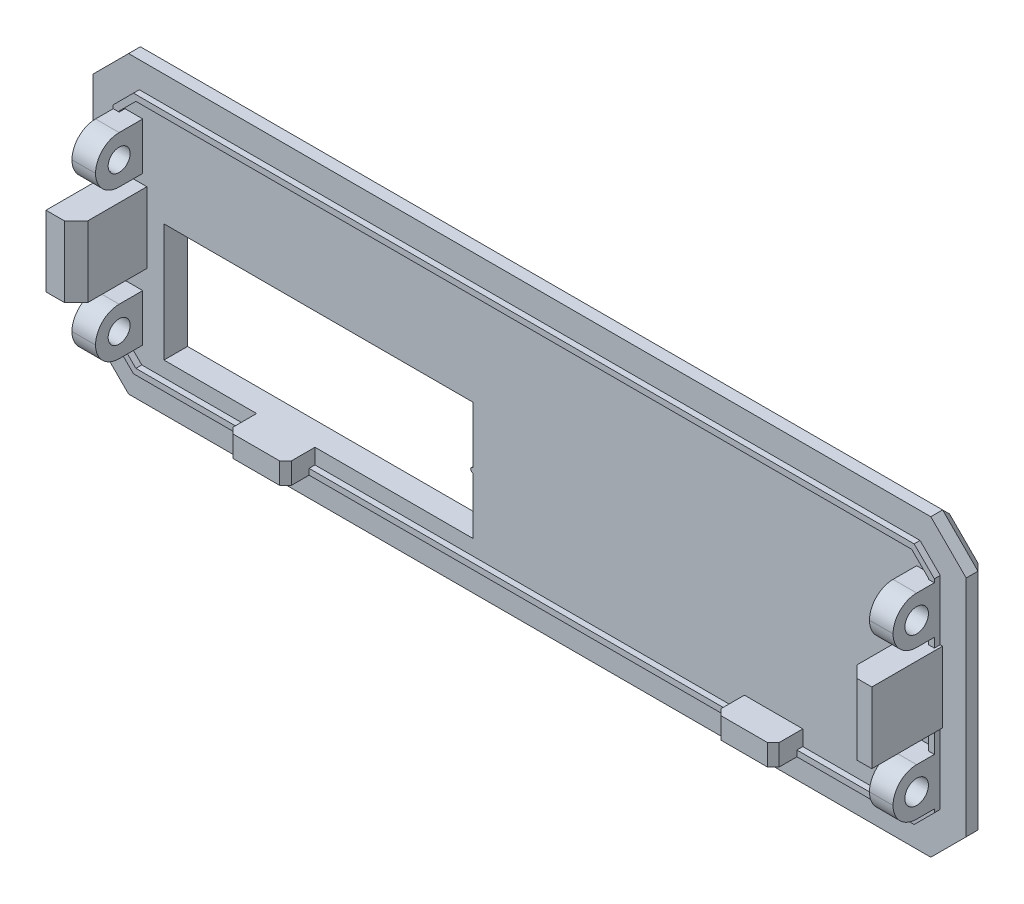
SolidWorks part; units mm, degrees
ref_plane "前视基准面" through (0, 0, 0) normal (0, 0, 1) x (1, 0, 0)
ref_plane "上视基准面" through (0, 0, 0) normal (0, 1, 0) x (1, 0, 0)
ref_plane "右视基准面" through (0, 0, 0) normal (1, 0, 0) x (0, 0, -1)
other "Configuration Table"
sketch "草图1" plane through (0, 0, 0) normal (0, 0, 1) x (1, 0, 0)
  line L0 (-39.7638, 4.7992) -> (-36.7638, 7.7992)
  line L5 (-36.7638, 7.7992) -> (31.2362, 7.7992)
  line L6 (-39.7638, 4.7992) -> (-39.7638, -14.2008)
  line L7 (-36.7638, -17.2008) -> (31.2362, -17.2008)
  line L8 (34.2362, 4.7992) -> (34.2362, -14.2008)
  line L9 (-39.7638, -14.2008) -> (-36.7638, -17.2008)
  line L10 (31.2362, -17.2008) -> (34.2362, -14.2008)
  line L11 (31.2362, 7.7992) -> (34.2362, 4.7992)
  point P0 (-39.7638, 7.7992)
  point P1 (34.2362, -17.2008)
  point P2 (-39.7638, -17.2008)
  point P3 (34.2362, 7.7992)
  dimension "D1" = 74
  dimension "D2" = 25
extrude "凸台-拉伸1" add sketch "草图1" along normal blind 2
chamfer "倒角1" distance 1 angle 45 8 edges at (-38.2638, 6.2992, 0) (-2.7638, -17.2008, 0) (-39.7638, -4.7008, 0) (-38.2638, -15.7008, 0) (32.7362, -15.7008, 0) (34.2362, -4.7008, 0) (32.7362, 6.2992, 0) (-2.7638, 7.7992, 0)
sketch "草图3" plane through (0, 0, 2) normal (0, 0, 1) x (1, 0, 0)
  line L0 (-36.7638, 7.7992) -> (31.2362, 7.7992) construction
  line L1 (-37.5638, 3.5992) -> (-35.5638, 3.5992)
  line L2 (-37.5638, 3.5992) -> (-37.5638, -0.4008)
  line L3 (-37.5638, -0.4008) -> (-35.5638, -0.4008)
  line L4 (-35.5638, 3.5992) -> (-35.5638, -0.4008)
  line L5 (-37.5638, -13.0008) -> (-35.5638, -13.0008)
  line L6 (-37.5638, -13.0008) -> (-37.5638, -9.0008)
  line L7 (-37.5638, -9.0008) -> (-35.5638, -9.0008)
  line L8 (-35.5638, -13.0008) -> (-35.5638, -9.0008)
  line L9 (32.0362, 3.5992) -> (30.0362, 3.5992)
  line L10 (32.0362, 3.5992) -> (32.0362, -0.4008)
  line L11 (32.0362, -0.4008) -> (30.0362, -0.4008)
  line L12 (30.0362, 3.5992) -> (30.0362, -0.4008)
  line L13 (32.0362, -13.0008) -> (30.0362, -13.0008)
  line L14 (32.0362, -13.0008) -> (32.0362, -9.0008)
  line L15 (32.0362, -9.0008) -> (30.0362, -9.0008)
  line L16 (30.0362, -13.0008) -> (30.0362, -9.0008)
  line L17 (-39.7638, -14.2008) -> (-39.7638, 4.7992) construction
  line L18 (34.2362, 4.7992) -> (34.2362, -14.2008) construction
  line L19 (31.2362, -17.2008) -> (-36.7638, -17.2008) construction
  dimension "D1" = 2
  dimension "D2" = 4
  dimension "D3" = 4.2
  dimension "D4" = 2.2
  dimension "D5" = 2.2
  dimension "D6" = 4.2
extrude "凸台-拉伸2" add sketch "草图3" along normal blind 4
fillet "圆角1" radius 2 8 edges at (31.0362, 3.5992, 6) (31.0362, -0.4008, 6) (31.0362, -9.0008, 6) (31.0362, -13.0008, 6) (-36.5638, -13.0008, 6) (-36.5638, -9.0008, 6) (-36.5638, 3.5992, 6) (-36.5638, -0.4008, 6)
sketch "草图4" plane through (32.0362, 0, 0) normal (1, 0, 0) x (0, 0, -1)
  circle A0 centre (-4, 1.5992) radius 1
  circle A1 centre (-4, -11.0008) radius 1
  dimension "D1" = 2
extrude "切除-拉伸1" cut sketch "草图4" against normal up to next (2 mm away) draft 2
sketch "草图5" plane through (-37.5638, 0, 0) normal (-1, 0, 0) x (0, 0, 1)
  circle A0 centre (4, 1.5992) radius 1
  circle A1 centre (4, -11.0008) radius 1
  dimension "D1" = 2
extrude "切除-拉伸2" cut sketch "草图5" against normal up to next (2 mm away) draft 2
sketch "草图8" plane through (0, 0, 2) normal (0, 0, 1) x (1, 0, 0)
  line L0 (-37.7638, 3.9708) -> (-37.7638, -13.3724) construction
  line L1 (-37.7638, -1.2008) -> (-35.2138, -1.2008)
  line L2 (-37.7638, -1.2008) -> (-37.7638, -7.2008)
  line L3 (-37.7638, -7.2008) -> (-35.2138, -7.2008)
  line L4 (-35.2138, -1.2008) -> (-35.2138, -7.2008)
  line L6 (32.2362, -13.3724) -> (32.2362, 3.9708) construction
  line L7 (32.2362, -1.2008) -> (29.9862, -1.2008)
  line L8 (32.2362, -1.2008) -> (32.2362, -7.2008)
  line L9 (32.2362, -7.2008) -> (29.9862, -7.2008)
  line L10 (29.9862, -1.2008) -> (29.9862, -7.2008)
  line L12 (-36.7638, -17.2008) -> (31.2362, -17.2008) construction
  dimension "D1" = 10
  dimension "D2" = 6
  dimension "D3" = 2.55
  dimension "D4" = 2.25
extrude "凸台-拉伸5" add sketch "草图8" along normal blind 6
chamfer "倒角3" distance 1 angle 45 2 edges at (29.9862, -4.2008, 8) (-35.2138, -4.2008, 8)
sketch "草图10" plane through (0, 0, 0) normal (0, 0, -1) x (-1, 0, 0)
  line L0 (36.7638, -17.2008) -> (-31.2362, -17.2008) construction
  line L1 (7.5638, -3.2008) -> (33.7638, -3.2008)
  line L2 (7.5638, -3.2008) -> (7.5638, -13.2008)
  line L3 (7.5638, -13.2008) -> (33.7638, -13.2008)
  line L4 (33.7638, -3.2008) -> (33.7638, -13.2008)
  line L5 (39.7638, 4.7992) -> (39.7638, -14.2008) construction
  dimension "D1" = 4
  dimension "D2" = 10
  dimension "D3" = 6
  dimension "D4" = 26.2
extrude "切除-拉伸3" cut sketch "草图10" against normal up to next
sketch "草图11" plane through (0, 0, 2) normal (0, 0, 1) x (1, 0, 0)
  line L8 (30.1178, 5.0992) -> (-35.6455, 5.0992)
  line L9 (-35.6455, 5.0992) -> (-37.0638, 3.6808)
  line L10 (-37.0638, 3.6808) -> (-37.0638, -13.0824)
  line L11 (-37.0638, -13.0824) -> (-35.6455, -14.5008)
  line L12 (-35.6455, -14.5008) -> (30.1178, -14.5008)
  line L13 (30.1178, -14.5008) -> (31.5362, -13.0824)
  line L14 (31.5362, -13.0824) -> (31.5362, 3.6808)
  line L15 (31.5362, 3.6808) -> (30.1178, 5.0992)
  line L16 (30.3249, 5.5992) -> (-35.8526, 5.5992)
  line L17 (-35.8526, 5.5992) -> (-37.5638, 3.8879)
  line L18 (-37.5638, 3.8879) -> (-37.5638, -13.2895)
  line L19 (-37.5638, -13.2895) -> (-35.8526, -15.0008)
  line L20 (-35.8526, -15.0008) -> (30.3249, -15.0008)
  line L21 (30.3249, -15.0008) -> (32.0362, -13.2895)
  line L22 (32.0362, -13.2895) -> (32.0362, 3.8879)
  line L23 (32.0362, 3.8879) -> (30.3249, 5.5992)
  line L24 (30.3249, 5.5992) -> (-35.8526, 5.5992)
  line L25 (-35.8526, 5.5992) -> (-37.5638, 3.8879)
  line L26 (-37.5638, 3.8879) -> (-37.5638, -13.2895)
  line L27 (-37.5638, -13.2895) -> (-35.8526, -15.0008)
  line L28 (-35.8526, -15.0008) -> (30.3249, -15.0008)
  line L29 (30.3249, -15.0008) -> (32.0362, -13.2895)
  line L30 (32.0362, -13.2895) -> (32.0362, 3.8879)
  line L31 (32.0362, 3.8879) -> (30.3249, 5.5992)
  dimension "D1" = 2.2
  dimension "D2" = 0.5
extrude "凸台-拉伸7" add sketch "草图11" along normal blind 0.5
sketch "草图12" plane through (0, 0, 2) normal (0, 0, 1) x (1, 0, 0)
  line L0 (20.4077, -13.2008) -> (15.4077, -13.2008) construction
  line L1 (15.4362, -13.2008) -> (20.3862, -13.2008)
  line L2 (15.4362, -13.2008) -> (15.4362, -15.0008)
  line L3 (15.4362, -15.0008) -> (20.3862, -15.0008)
  line L4 (20.3862, -13.2008) -> (20.3862, -15.0008)
  line L6 (34.2362, -14.2008) -> (34.2362, 4.7992) construction
  line L7 (-33.7638, -13.2008) -> (-7.5638, -13.2008) construction
  line L8 (-25.9138, -13.2008) -> (-20.9638, -13.2008)
  line L9 (-25.9138, -13.2008) -> (-25.9138, -15.0008)
  line L10 (-25.9138, -15.0008) -> (-20.9638, -15.0008)
  line L11 (-20.9638, -13.2008) -> (-20.9638, -15.0008)
  line L13 (-39.7638, 4.7992) -> (-39.7638, -14.2008) construction
  line L14 (-35.8526, -15.0008) -> (30.3249, -15.0008) construction
  dimension "D1" = 13.85
  dimension "D2" = 4.95
  dimension "D3" = 13.85
extrude "凸台-拉伸8" add sketch "草图12" along normal blind 2.5
chamfer "倒角4" distance 0.5 angle 45 4 edges at (-25.9138, -14.1008, 4.5) (-20.9638, -14.1008, 4.5) (20.3862, -14.1008, 4.5) (15.4362, -14.1008, 4.5)
sketch "草图13" plane through (0, 0, 0) normal (0, 0, -1) x (-1, 0, 0)
  line L0 (7.5638, -3.2008) -> (7.5638, -13.2008) construction
  circle A0 centre (7.5638, -8.2008) radius 0.2
  dimension "D1" = 0.4
extrude "凸台-拉伸9" add sketch "草图13" against normal blind 2
